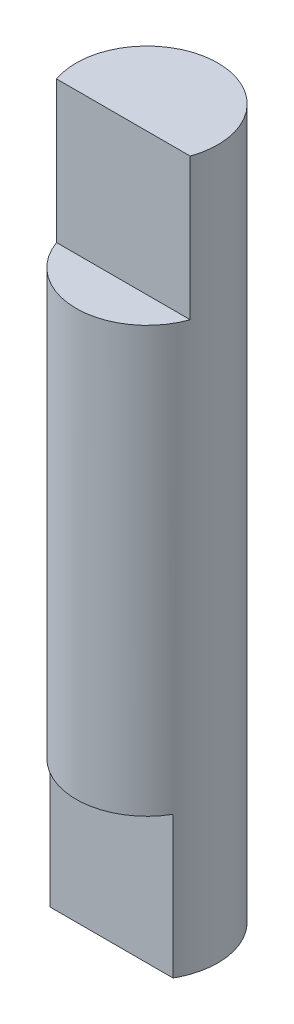
SolidWorks part; units mm, degrees
ref_plane "Alzado" through (0, 0, 0) normal (0, 0, 1) x (1, 0, 0)
ref_plane "Planta" through (0, 0, 0) normal (0, 1, 0) x (1, 0, 0)
ref_plane "Vista lateral" through (0, 0, 0) normal (1, 0, 0) x (0, 0, -1)
sketch "Croquis1" plane through (0, 0, 0) normal (0, 1, 0) x (1, 0, 0)
  circle A0 centre (0, 0) radius 3
  dimension "D1" = 6
extrude "Saliente-Extruir1" add sketch "Croquis1" along normal mid plane 30
sketch "Croquis3" plane through (0, 15, 0) normal (0, 1, 0) x (1, 0, 0)
  line L1 (-3.8744, -1) -> (4.3498, -1)
  line L2 (-3.8744, -1) -> (-3.8744, -3)
  line L3 (-3.8744, -3) -> (4.3498, -3)
  line L4 (4.3498, -1) -> (4.3498, -3)
  circle A0 centre (0, 0) radius 3 construction
  dimension "D1" = 2
  dimension "D2" = 1
extrude "Cortar-Extruir2" cut sketch "Croquis3" against normal blind 6 and the other way through all
sketch "Croquis4" plane through (0, 15, 0) normal (0, 1, 0) x (1, 0, 0)
  point P0 (0, 0)
ref_axis "Eje1" through (0, 15, 0) along (0, -1, 0)
sketch "Croquis7" plane through (0, -15, 0) normal (0, -1, 0) x (1, 0, 0)
  line L0 (-2.5981, 1.5) -> (2.5981, 1.5)
  circle A0 centre (0, 0) radius 3 construction
  arc A1 (2.5981, 1.5) -> (-2.5981, 1.5) centre (0, 0) ccw
  dimension "D1" = 1.5
extrude "Cortar-Extruir3" cut sketch "Croquis7" against normal blind 6
